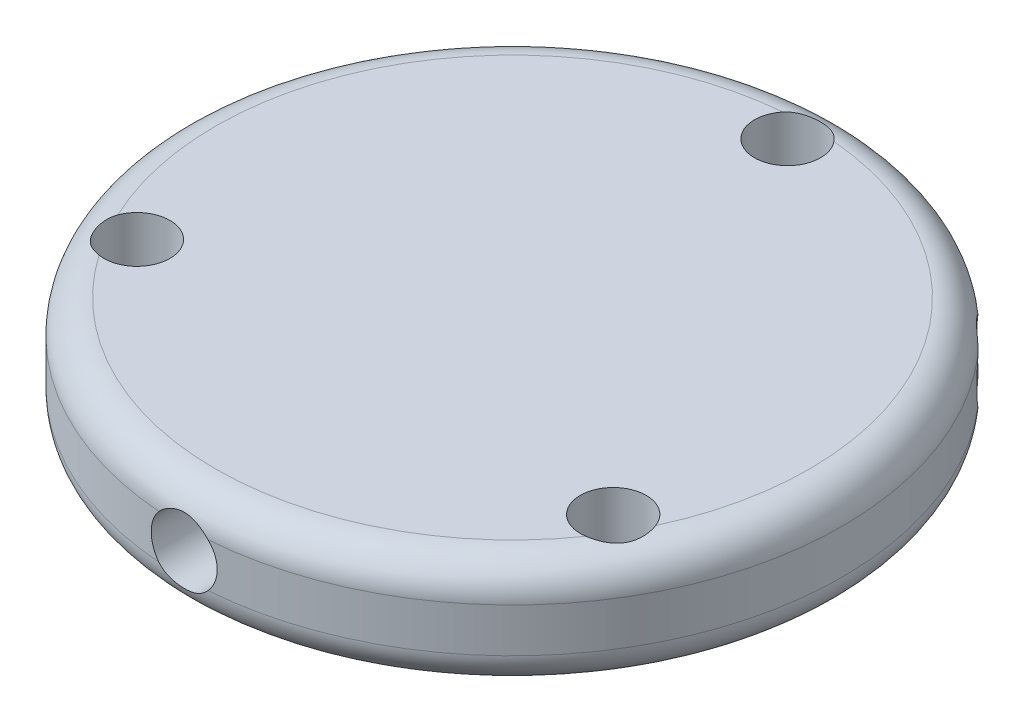
SolidWorks part; units mm, degrees
material "ABS"
ref_plane "Front Plane" through (0, 0, 0) normal (0, 0, 1) x (1, 0, 0)
ref_plane "Top Plane" through (0, 0, 0) normal (0, 1, 0) x (1, 0, 0)
ref_plane "Right Plane" through (0, 0, 0) normal (1, 0, 0) x (0, 0, -1)
sketch "Sketch1" plane through (0, 0, 0) normal (0, 1, 0) x (1, 0, 0)
  circle A0 centre (0, 0) radius 30
  circle A1 centre (0, 25) radius 3
  circle A2 centre (21.6506, -12.5) radius 3
  circle A3 centre (-21.6506, -12.5) radius 3
  point P12 (0, 0)
  dimension "D1" = 60
  dimension "D2" = 6
  dimension "D3" = 25
  dimension "D4" = 3
extrude "Boss-Extrude1" add sketch "Sketch1" along normal blind 10
sketch "Sketch3" plane through (0, 0, 0) normal (0, 0, 1) x (1, 0, 0)
  circle A0 centre (0, 5) radius 3
  dimension "D2" = 6
  dimension "D1" = 5
extrude "Cut-Extrude1" cut sketch "Sketch3" along normal through all
pattern_circular "CirPattern1" count 8 over 360 about axis through (0, 10, 0) along (0, 1, 0) skipping 1, 2, 4, 6, 7 of "Cut-Extrude1"
fillet "Fillet1" radius 3 2 edges at (0, 0, 30) (0, 10, 30)
